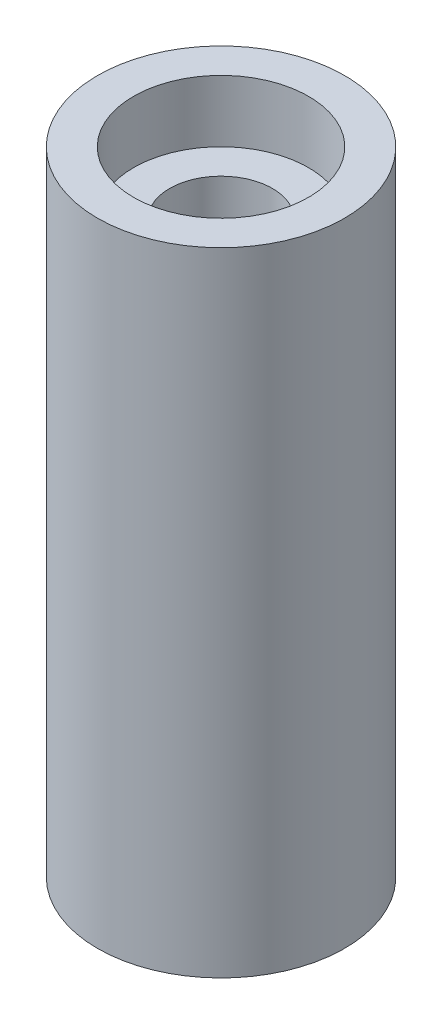
SolidWorks part; units mm, degrees
ref_plane "Front Plane" through (0, 0, 0) normal (0, 0, 1) x (1, 0, 0)
ref_plane "Top Plane" through (0, 0, 0) normal (0, 1, 0) x (1, 0, 0)
ref_plane "Right Plane" through (0, 0, 0) normal (1, 0, 0) x (0, 0, -1)
sketch "Sketch1" plane through (0, 0, 0) normal (0, 1, 0) x (1, 0, 0)
  circle A0 centre (0, 0) radius 38.1
extrude "Boss-Extrude1" add sketch "Sketch1" along normal blind 97.5 and the other way blind 97.5
sketch "Sketch2" plane through (0, 97.5, 0) normal (0, 1, 0) x (1, 0, 0)
  circle A0 centre (0, 0) radius 26.9875
  dimension "D1" = 53.975
extrude "Cut-Extrude1" cut sketch "Sketch2" against normal blind 19.05 contours A0
mirror "Mirror1" about plane through (0, 0, 0) normal (0, 1, 0) of "Cut-Extrude1"
sketch "Sketch3" plane through (0, 78.45, 0) normal (0, 1, 0) x (1, 0, 0)
  circle A0 centre (0, 0) radius 15.875
  dimension "D1" = 31.75
extrude "Cut-Extrude2" cut sketch "Sketch3" against normal through all
